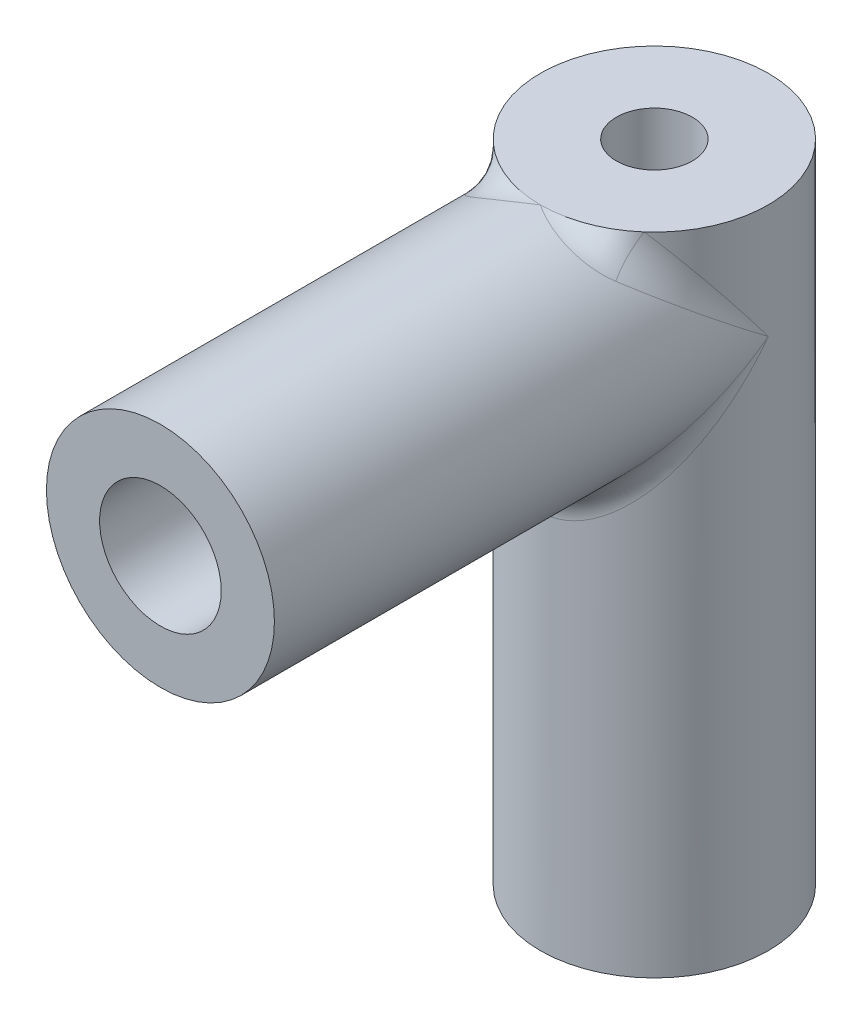
SolidWorks part; units mm, degrees
ref_plane "Front Plane" through (0, 0, 0) normal (0, 0, 1) x (1, 0, 0)
ref_plane "Top Plane" through (0, 0, 0) normal (0, 1, 0) x (1, 0, 0)
ref_plane "Right Plane" through (0, 0, 0) normal (1, 0, 0) x (0, 0, -1)
sketch "Sketch1" plane through (0, 0, 0) normal (0, 1, 0) x (1, 0, 0)
  circle A0 centre (0, 0) radius 1
  circle A1 centre (0, 0) radius 3
  dimension "D1" = 2
  dimension "D2" = 6
extrude "Boss-Extrude1" add sketch "Sketch1" along normal blind 14 separate body contours A1
sketch "Sketch2" plane through (0, 0, 0) normal (0, 0, 1) x (1, 0, 0)
  line L0 (3, 14) -> (-3, 14) construction
  circle A0 centre (0, 11) radius 1.6
  circle A1 centre (0, 11) radius 3
  point P7 (0, 8)
  dimension "D1" = 3.2
  dimension "D2" = 6
extrude "Boss-Extrude2" add sketch "Sketch2" along normal blind 13 contours A1
sketch "Sketch4" plane through (0, 0, 0) normal (0, -1, 0) x (1, 0, 0)
  circle A0 centre (0, 0) radius 3 construction
  circle A1 centre (0, 0) radius 3
extrude "option1" add sketch "Sketch4" along normal blind 3
sketch "Sketch3" [suppressed] plane through (0, 0, 0) normal (0, -1, 0) x (1, 0, 0)
  circle A0 centre (0, 0) radius 4.5
  dimension "D1" = 9
extrude "option2" [suppressed] add sketch "Sketch3" against normal blind 1.5
extrude "Cut-Extrude1" cut sketch "Sketch1<3>" along normal through all both and the other way through all contours A0
sketch "Sketch1<3>" plane through (0, 0, 0) normal (0, 1, 0) x (1, 0, 0) same geometry as "Sketch1"
extrude "Cut-Extrude2" cut sketch "Sketch2<3>" against normal blind 5 from surface contours A0 starting at face at (3, 11, 13)
sketch "Sketch2<3>" plane through (0, 0, 0) normal (0, 0, 1) x (1, 0, 0) same geometry as "Sketch2"
fillet "Fillet1" radius 1 3 edges at (0, 8, 3) (2.1213, 13.1213, 2.1213) (-2.1213, 13.1213, 2.1213)
